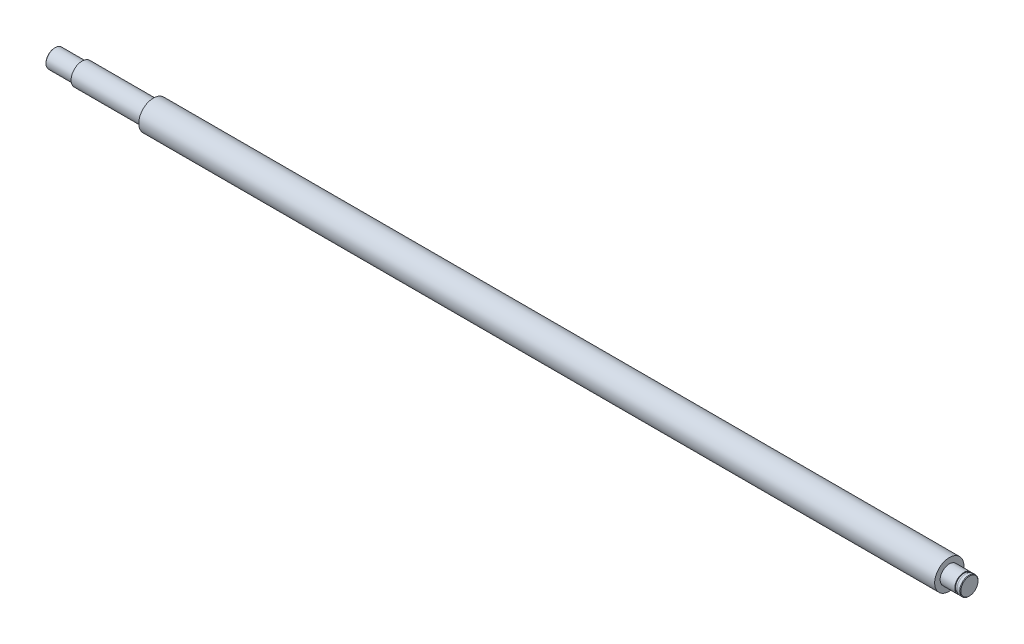
SolidWorks part; units mm, degrees
material "Легированная сталь"
ref_plane "Спереди" through (0, 0, 0) normal (0, 0, 1) x (1, 0, 0)
ref_plane "Сверху" through (0, 0, 0) normal (0, 1, 0) x (1, 0, 0)
ref_plane "Справа" through (0, 0, 0) normal (1, 0, 0) x (0, 0, -1)
sketch "Эскиз1" plane through (0, 0, 0) normal (0, 0, 1) x (1, 0, 0)
  line L0 (-250, 0) -> (250, 0)
  line L1 (-250, 0) -> (-250, 5)
  line L2 (-250, 5) -> (-235, 5)
  line L3 (-235, 5) -> (-235, 6)
  line L4 (-235, 6) -> (-196, 6)
  line L5 (-196, 6) -> (-196, 8)
  line L6 (-196, 8) -> (239, 8)
  line L7 (239, 8) -> (239, 5)
  line L8 (239, 5) -> (250, 5)
  line L9 (250, 5) -> (250, 0)
  dimension "D1" = 500
  dimension "D2" = 11
  dimension "D3" = 5
  dimension "D4" = 15
  dimension "D5" = 5
  dimension "D8" = 8
  dimension "D6" = 39
  dimension "D7" = 6
revolve "Повернуть1" add sketch "Эскиз1" angle 360 about L0
cosmetic thread "Условное изображение резьбы2" parameters "D1"=14, "D2"=10.072
sketch "Эскиз2" plane through (0, 0, 0) normal (0, 0, 1) x (1, 0, 0)
  line L0 (250, 5) -> (239, 5) construction
  line L1 (247, 5) -> (248.15, 5)
  line L2 (247, 5) -> (247, 4.6)
  line L3 (247, 4.6) -> (248.15, 4.6)
  line L4 (248.15, 5) -> (248.15, 4.6)
  line L5 (239, 0) -> (250, 0) construction
  line L6 (239, -8) -> (239, 8) construction
  line L7 (250, -5) -> (250, 5) construction
  dimension "D1" = 1.15
  dimension "D2" = 9.15
  dimension "D3" = 4.6
revolve "Вырез-Повернуть1" cut sketch "Эскиз2" angle 360 about L5
sketch "Эскиз3" plane through (-250, 0, 0) normal (-1, 0, 0) x (0, 0, 1)
  circle A0 centre (0, 0) radius 8
  dimension "D1" = 16
curve "Спираль1" pitch 5 height 250 turns 50
sketch "Эскиз4" plane through (0, 0, 0) normal (0, 0, 1) x (1, 0, 0)
  line L0 (-250, 5) -> (-250, -5) construction
  line L2 (-247.6, 7.8) -> (-247.4, 7.8)
  line L3 (-247.6, 7.8) -> (-247.6, 8.4)
  line L4 (-247.6, 8.4) -> (-247.4, 8.4)
  line L5 (-247.4, 7.8) -> (-247.4, 8.4)
  circle A0 centre (-250, 8.4) radius 1.9
  point P2 (-250, 0)
  point P10 (-247.5, 7.8)
  dimension "D1" = 3.8
  dimension "D2" = 8.4
  dimension "D3" = 0.2
  dimension "D4" = 2.5
  dimension "D5" = 7.8
sweep "Вырез-По траектории1" [suppressed] cut profiles "Эскиз4" path "Спираль1"
fillet "Скругление1" [suppressed] radius 0.2
chamfer "Фаска1" distance 0.3 angle 45 2 edges at (-250, 0, 5) (250, 0, 5)
equation "\"SBR16.Length.X\"= 600мм"
equation "\"SBR16.Length.Y\"= 500мм"
equation "\"SBR16.Length.Z\"= 250мм"
equation "\"D1@Эскиз1\"= \"SBR16.Length.Y\""
